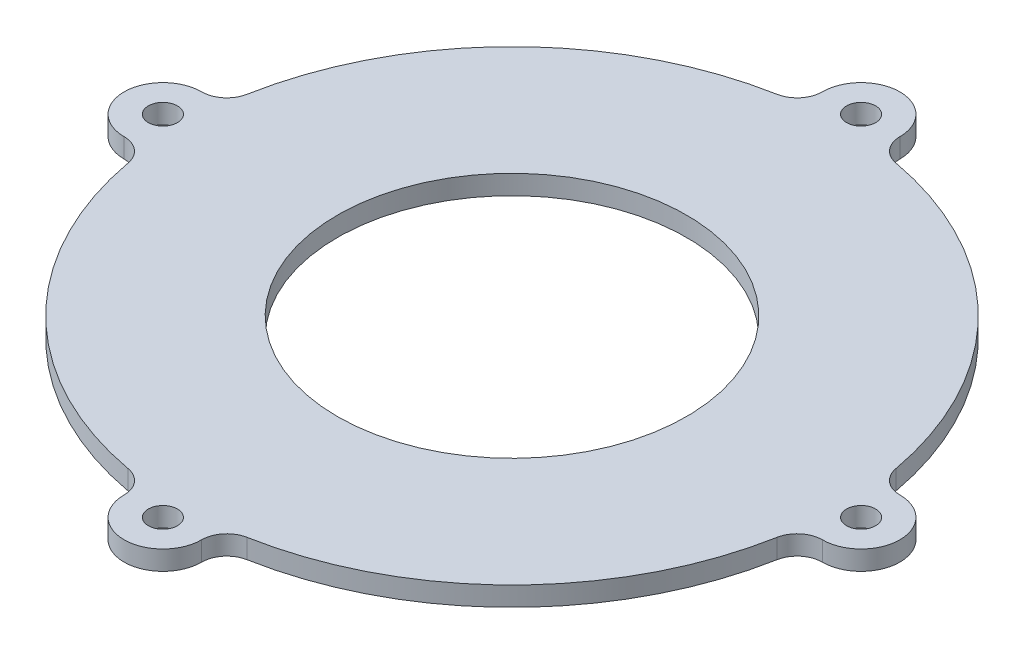
SolidWorks part; units mm, degrees
ref_plane "Front Plane" through (0, 0, 0) normal (0, 0, 1) x (1, 0, 0)
ref_plane "Top Plane" through (0, 0, 0) normal (0, 1, 0) x (1, 0, 0)
ref_plane "Right Plane" through (0, 0, 0) normal (1, 0, 0) x (0, 0, -1)
sketch "Sketch1" plane through (0, 0, 0) normal (0, 1, 0) x (1, 0, 0)
  line L0 (0, 0) -> (15.2441, 0) construction
  arc A0 (33.4426, -6.1311) -> (36, -4) centre (36, -6.6) cw
  arc A1 (33.4426, 6.1311) -> (36, 4) centre (36, 6.6) ccw
  arc A2 (-6.1311, -33.4426) -> (-4, -36) centre (-6.6, -36) cw
  arc A3 (6.1311, -33.4426) -> (4, -36) centre (6.6, -36) ccw
  arc A4 (-33.4426, 6.1311) -> (-36, 4) centre (-36, 6.6) cw
  arc A5 (-33.4426, -6.1311) -> (-36, -4) centre (-36, -6.6) ccw
  arc A6 (6.1311, 33.4426) -> (4, 36) centre (6.6, 36) cw
  arc A7 (-6.1311, 33.4426) -> (-4, 36) centre (-6.6, 36) ccw
  point P6 (-8.244, -50.1776)
  point P7 (0, 0)
  point P30 (0, 0)
  circle B0 centre (0, 0) radius 18
  circle B1 centre (0, 0) radius 25
  circle B2 centre (0, 0) radius 31
  circle B3 centre (0, 0) radius 34
  circle B4 centre (36, 0) radius 1.5
  arc B5 (33.8333, -3.3624) -> (33.8333, 3.3624) centre (36, 0) ccw
  arc B6 (-3.3624, -33.8333) -> (3.3624, -33.8333) centre (0, -36) ccw
  circle B7 centre (0, -36) radius 1.5
  arc B8 (-33.8333, 3.3624) -> (-33.8333, -3.3624) centre (-36, 0) ccw
  circle B9 centre (-36, 0) radius 1.5
  arc B10 (3.3624, 33.8333) -> (-3.3624, 33.8333) centre (0, 36) ccw
  circle B11 centre (0, 36) radius 1.5
  dimension "D1" = 4
sketch_block_instance "Block1-1"
sketch_block "Block1" parameters "D2"=4, "D4"=3, "D5"=32, "D1"=32, "D3"=36
extrude "Boss-Extrude1" add sketch "Sketch1" along normal blind 2 contours B2 B1 | B1 B0 | B3 B2 | B3 B5 B4 | B3 B6 B7 | B3 B8 B9 | B3 B10 B11 | B5 A1 B3 | B5 B3 A0 | B10 B3 A6 | B10 A7 B3 | B6 A3 B3 | B6 B3 A2 | B8 B3 A4 | B8 A5 B3 region at (34.2416, 0, 4.2569) region at (23.3616, 0, 23.3616) region at (34.8992, 0, 3.7404) region at (4.2569, 0, 34.2416) region at (34.2416, 0, -4.2569) region at (0, 0, 39.899) region at (-4.2569, 0, 34.2416) region at (4.2569, 0, -34.2416) region at (3.7404, 0, -34.8992) region at (-34.2416, 0, 4.2569) region at (-4.2569, 0, -34.2416) region at (-39.899, 0, 0) region at (-34.2416, 0, -4.2569) region at (-24.2929, 0, 0) region at (-30.1232, 0, 0)
extrude "Boss-Extrude2" add sketch "Sketch1<3>" against normal blind 1 contours B2 B1 region at (-30.1232, 0, 0)
sketch "Sketch1<3>" plane through (0, 0, 0) normal (0, 1, 0) x (1, 0, 0) same geometry as "Sketch1"
